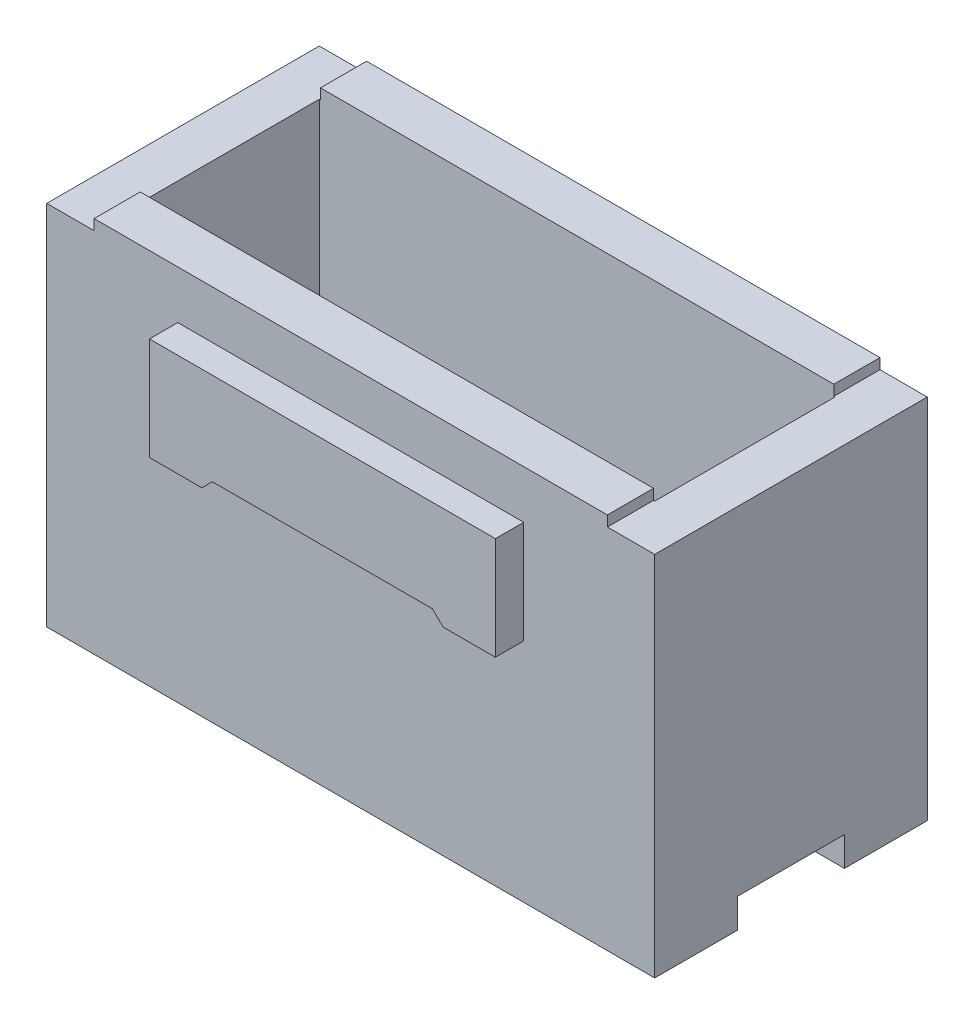
SolidWorks part; units mm, degrees
material "ABS"
ref_plane "Front Plane" through (0, 0, 0) normal (0, 0, 1) x (1, 0, 0)
ref_plane "Top Plane" through (0, 0, 0) normal (0, 1, 0) x (1, 0, 0)
ref_plane "Right Plane" through (0, 0, 0) normal (1, 0, 0) x (0, 0, -1)
sketch "Sketch1" plane through (0, 0, 0) normal (0, 0, 1) x (1, 0, 0)
  line L1 (14.5, 9) -> (-14.5, 9)
  line L2 (14.5, 9) -> (14.5, -9)
  line L3 (14.5, -9) -> (-14.5, -9)
  line L4 (-14.5, 9) -> (-14.5, -9)
  line L5 (14.5, 9) -> (-14.5, -9) construction
  line L6 (14.5, -9) -> (-14.5, 9) construction
  point P0 (0, 0)
  dimension "D1" = 29
  dimension "D2" = 18
extrude "Boss-Extrude1" add sketch "Sketch1" along normal blind 13
sketch "Sketch2" plane through (0, 0, 13) normal (0, 0, 1) x (1, 0, 0)
  line L0 (-5.75, 1.8) -> (-5.25, 2.3)
  line L1 (8.25, 6.7) -> (-8.25, 6.7)
  line L2 (8.25, 6.7) -> (8.25, 1.8)
  line L3 (8.25, 1.8) -> (5.75, 1.8)
  line L4 (-8.25, 6.7) -> (-8.25, 1.8)
  line L5 (8.25, 6.7) -> (-8.25, 1.8) construction
  line L6 (8.25, 1.8) -> (-8.25, 6.7) construction
  line L7 (-5.25, 2.3) -> (5.25, 2.3)
  line L8 (5.25, 2.3) -> (5.75, 1.8)
  line L9 (-5.75, 1.8) -> (-8.25, 1.8)
  line L10 (14.5, 9) -> (-14.5, 9) construction
  point P0 (0, 4.25)
  point P7 (0, 2.3)
  dimension "D1" = 16.5
  dimension "D2" = 4.9
  dimension "D3" = 6.7
  dimension "D4" = 3
  dimension "D5" = 2.5
extrude "Boss-Extrude2" add sketch "Sketch2" along normal blind 1.35 and the other way blind 14.35
sketch "Sketch3" plane through (0, -9, 0) normal (0, -1, 0) x (1, 0, 0)
  line L0 (0, -6.5) -> (0, 6.5) construction
  line L1 (-2.55, -6.5) -> (-2.55, 6.5)
  line L2 (2.55, -6.5) -> (2.55, 6.5)
  line L3 (-14.5, 13) -> (-14.5, 0) construction
  line L4 (-21, 6.5) -> (-8, 6.5) construction
  line L5 (-21, 9.05) -> (-8, 9.05)
  line L6 (-21, 3.95) -> (-8, 3.95)
  line L7 (0, -8.635) -> (0, 8.635) construction
  line L8 (21, 6.5) -> (8, 6.5) construction
  line L9 (21, 9.05) -> (8, 9.05)
  line L10 (21, 3.95) -> (8, 3.95)
  arc A0 (-2.55, -6.5) -> (2.55, -6.5) centre (0, -6.5) ccw
  arc A1 (2.55, 6.5) -> (-2.55, 6.5) centre (0, 6.5) ccw
  arc A2 (-21, 9.05) -> (-21, 3.95) centre (-21, 6.5) ccw
  arc A3 (-8, 3.95) -> (-8, 9.05) centre (-8, 6.5) ccw
  arc A4 (21, 9.05) -> (21, 3.95) centre (21, 6.5) cw
  arc A5 (8, 3.95) -> (8, 9.05) centre (8, 6.5) cw
  point P2 (0, 0)
  point P11 (-14.5, 6.5)
  point P12 (-14.5, 6.5)
  point P22 (14.5, 6.5)
  dimension "D1" = 5.1
extrude "Cut-Extrude1" cut sketch "Sketch3" against normal blind 1.4
shell "Shell1" thickness 2.2 removed face at (0, 9, 6.5)
sketch "Sketch4" plane through (0, -7.6, 0) normal (0, -1, 0) x (1, 0, 0)
  circle A0 centre (0, 6.5) radius 1.05
  circle A1 centre (-8, 6.5) radius 1.05
  circle A2 centre (8, 6.5) radius 1.05
  dimension "D1" = 2.1
extrude "Cut-Extrude2" cut sketch "Sketch4" against normal through all
sketch "Sketch5" plane through (0, 9, 0) normal (0, 1, 0) x (1, 0, 0)
  line L0 (14.5, -13) -> (-14.5, -13) construction
  line L1 (-14.5, 0) -> (-12.2425, 0)
  line L2 (-14.5, 0) -> (-14.5, -13)
  line L3 (-14.5, -13) -> (-12.2425, -13)
  line L4 (-12.2425, 0) -> (-12.2425, -13)
  line L5 (0, -8.635) -> (0, 8.635) construction
  line L6 (14.5, -13) -> (12.2425, -13)
  line L7 (12.2425, 0) -> (12.2425, -13)
  line L8 (14.5, 0) -> (12.2425, 0)
  line L9 (14.5, 0) -> (14.5, -13)
extrude "Cut-Extrude3" cut sketch "Sketch5" against normal blind 0.5
